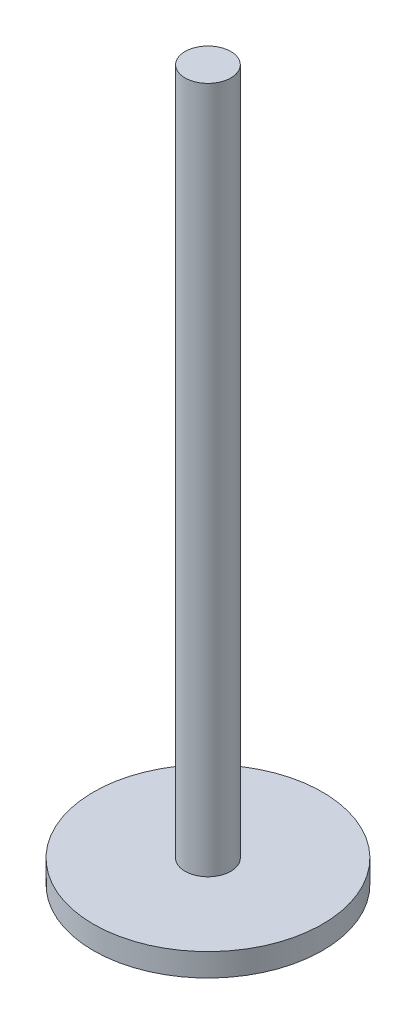
SolidWorks part; units mm, degrees
ref_plane "Front Plane" through (0, 0, 0) normal (0, 0, 1) x (1, 0, 0)
ref_plane "Top Plane" through (0, 0, 0) normal (0, 1, 0) x (1, 0, 0)
ref_plane "Right Plane" through (0, 0, 0) normal (1, 0, 0) x (0, 0, -1)
sketch "Sketch1" plane through (0, 0, 0) normal (0, 1, 0) x (1, 0, 0)
  circle A0 centre (0, 0) radius 2
  circle A1 centre (0, 0) radius 0.4
  dimension "D1" = 4
  dimension "D2" = 0.8
extrude "Boss-Extrude1" add sketch "Sketch1" against normal blind 0.4 contours A0
extrude "Boss-Extrude2" add sketch "Sketch1<3>" along normal blind 12 contours A1 region at (0, 0, 0)
sketch "Sketch1<3>" plane through (0, 0, 0) normal (0, 1, 0) x (1, 0, 0) same geometry as "Sketch1"
